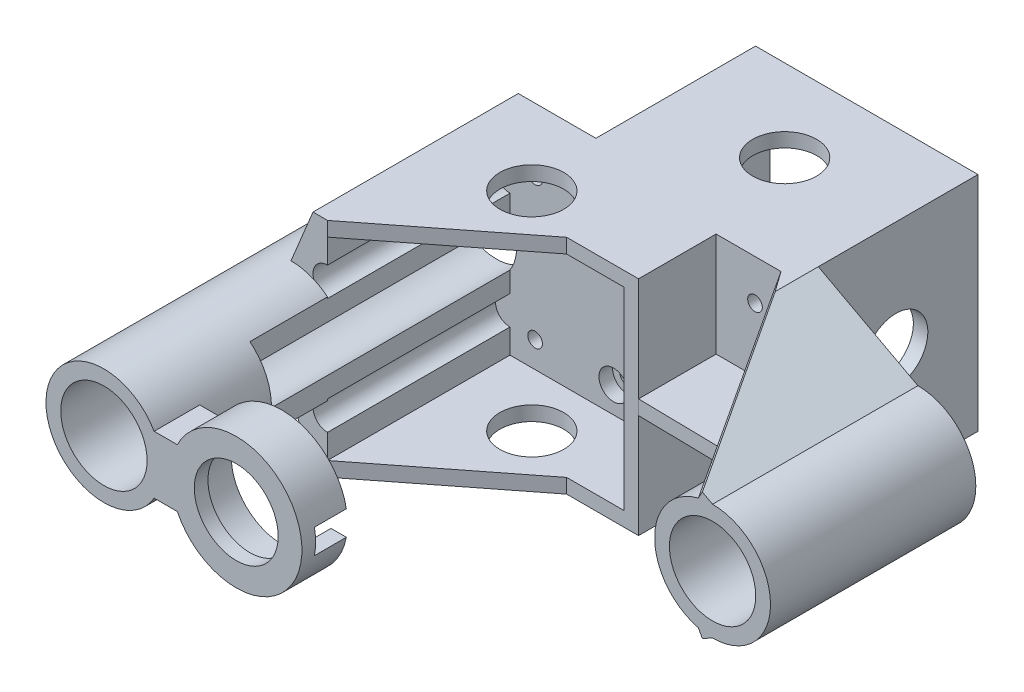
SolidWorks part; units mm, degrees
ref_plane "Front" through (0, 0, 0) normal (0, 0, 1) x (1, 0, 0)
ref_plane "Top" through (0, 0, 0) normal (0, 1, 0) x (1, 0, 0)
ref_plane "Right" through (0, 0, 0) normal (1, 0, 0) x (0, 0, -1)
sketch "Sketch4" plane through (0, 0, 0) normal (0, 0, 1) x (1, 0, 0)
  line L0 (0, -42.8625) -> (0, 41.275) construction
  line L1 (-47.9, -15.5) -> (-78.9, 15.5) construction
  line L2 (-78.9, -15.5) -> (-47.9, 15.5) construction
  line L3 (-39.225, 44.5615) -> (-39.225, -66.5635) construction
  line L4 (-70.575, 44.5615) -> (-70.575, -66.5635) construction
  line L8 (-61.7, 15.5) -> (-30.7, -15.5) construction
  line L9 (-30.7, 15.5) -> (-61.7, -15.5) construction
  line L11 (-30.7, 36.624) -> (-30.7, -53.8635) construction
  line L12 (45, 0) -> (-163.2133, 0) construction
  line L13 (-61.7, 36.624) -> (-61.7, -53.8635) construction
  line L14 (-47.9, 36.624) -> (-47.9, -53.8635) construction
  line L15 (-78.9, 36.624) -> (-78.9, -53.8635) construction
  line L16 (-111.9728, 15.5) -> (1.0464, 15.5) construction
  line L17 (-111.9728, -15.5) -> (1.0464, -15.5) construction
  line L18 (-25, -66.5635) -> (-25, 44.5615) construction
  line L19 (-67.4, -66.5635) -> (-67.4, 44.5615) construction
  line L20 (-42.4, 44.5615) -> (-42.4, -66.5635) construction
  line L21 (-84.4, -66.5635) -> (-84.4, 44.5615) construction
  line L22 (7.0897, -21.2) -> (-132.9126, -21.2) construction
  line L23 (7.0897, 21.2) -> (-132.9126, 21.2) construction
  line L24 (12.1749, -24.375) -> (-137.3728, -24.375) construction
  line L25 (12.1749, 24.375) -> (-137.3728, 24.375) construction
  line L26 (-87.575, 44.5615) -> (-87.575, -66.5635) construction
  line L27 (-21.825, 44.5615) -> (-21.825, -66.5635) construction
  circle A0 centre (0, 0) radius 12.7 construction
  circle A1 centre (0, 0) radius 15.875 construction
  circle A2 centre (0, 0) radius 9.46 construction
  circle A3 centre (-92.4, 0) radius 9.46 construction
  arc A4 (-92.4, 12.7) -> (-92.4, -12.7) centre (-92.4, 0) ccw construction
  circle A5 centre (27.62, 0) radius 9.46 construction
  circle A6 centre (27.62, 0) radius 12.7 construction
  circle A7 centre (-120.0175, 0) radius 9.46 construction
  circle A8 centre (-120.0175, 0) radius 12.7 construction
  point P3 (0, 0)
  point P6 (-47.9, -15.5)
  point P11 (-92.4, 0)
  point P12 (-47.9, 15.5)
  point P13 (-46.2, 0)
  point P14 (-78.9, 15.5)
  point P15 (-78.9, -15.5)
  point P61 (-63.4, 0)
  point P65 (27.62, 0)
  point P66 (-120.0175, 0)
  dimension "D20" = 3.175
  dimension "D18" = 29
  dimension "D26" = 73.82
  dimension "D27" = 63.4
  dimension "D2" = 31
  dimension "D3" = 25
  dimension "D4" = 31
  dimension "D5" = 21.825
  dimension "D6" = 15.5
  dimension "D7" = 15.5
  dimension "D8" = 5.7
  dimension "D9" = 5.7
  dimension "D10" = 5.5
  dimension "D11" = 5.5
  dimension "D12" = 5.7
  dimension "D13" = 5.7
  dimension "D14" = 3.175
  dimension "D15" = 3.175
  dimension "D16" = 3.175
  dimension "D17" = 3.175
  dimension "D19" = 3.175
  dimension "D21" = 3.175
  dimension "D22" = 46.2
  dimension "D23" = 46.2
  dimension "D24" = 58.32
  dimension "D25" = 147.6375
sketch "Sketch5" plane through (0, 0, 0) normal (0, 0, 1) x (1, 0, 0)
  line L0 (-21.825, -24.375) -> (0, -12.7)
  line L1 (12.1749, -24.375) -> (-137.3728, -24.375) construction
  line L2 (-21.825, 44.5615) -> (-21.825, -66.5635) construction
  line L3 (0, -42.8625) -> (0, 41.275) construction
  line L4 (12.1749, 24.375) -> (-137.3728, 24.375) construction
  line L5 (-21.825, 24.375) -> (0, 12.7)
  line L7 (-92.4, 12.7) -> (-87.575, 24.375)
  line L8 (-87.575, 44.5615) -> (-87.575, -66.5635) construction
  line L9 (-87.575, 24.375) -> (-21.825, 24.375)
  line L10 (-87.575, -24.375) -> (-92.4, -12.7)
  line L11 (-87.575, -24.375) -> (-21.825, -24.375)
  circle A0 centre (0, 0) radius 12.7 construction
  arc A1 (0, 12.7) -> (0, -12.7) centre (0, 0) cw
  circle A2 centre (0, 0) radius 9.46
  circle A3 centre (-92.4, 0) radius 9.46
  arc A4 (-92.4, 12.7) -> (-92.4, -12.7) centre (-92.4, 0) ccw
  circle A6 centre (-30.7, 15.5) radius 1.6
  circle A7 centre (-30.7, -15.5) radius 1.6
  circle A8 centre (-47.9, -15.5) radius 1.6
  circle A9 centre (-47.9, 15.5) radius 1.6
  circle A10 centre (-61.7, 15.5) radius 1.6
  circle A11 centre (-78.9, 15.5) radius 1.6
  circle A12 centre (-78.9, -15.5) radius 1.6
  circle A13 centre (-61.7, -15.5) radius 1.6
  arc A15 (-92.4, 12.7) -> (-92.4, -12.7) centre (-92.4, 0) ccw construction
extrude "Extrude1" add sketch "Sketch5" along normal blind 5
sketch "Sketch6" plane through (0, 0, 5) normal (0, 0, 1) x (1, 0, 0)
  line L0 (-84.4, -21.2) -> (-42.4, -21.2)
  line L1 (-84.4, -66.5635) -> (-84.4, 44.5615) construction
  line L2 (7.0897, -21.2) -> (-132.9126, -21.2) construction
  line L3 (-42.4, 44.5615) -> (-42.4, -66.5635) construction
  line L4 (-42.4, -21.2) -> (-42.4, 21.2)
  line L5 (7.0897, 21.2) -> (-132.9126, 21.2) construction
  line L6 (-42.4, 21.2) -> (-84.4, 21.2)
  line L7 (-39.225, 24.375) -> (-87.575, 24.375)
  line L9 (-39.225, 44.5615) -> (-39.225, -66.5635) construction
  line L10 (12.1749, 24.375) -> (-137.3728, 24.375) construction
  line L11 (-12.601, 1.5825) -> (-39.225, 1.5825)
  line L12 (-39.225, -24.375) -> (-87.575, -24.375)
  line L13 (-84.4, 21.2) -> (-84.4, 15.8916)
  line L14 (-84.4, -9.5084) -> (-84.4, -5.0489)
  line L16 (-87.575, 24.375) -> (-92.4, 12.7)
  line L17 (-87.575, -24.375) -> (-92.4, -12.7)
  line L19 (-84.4, 9.5416) -> (-84.4, 5.0489)
  line L20 (-84.4, -21.2) -> (-84.4, -15.8584)
  line L24 (-39.225, -1.5851) -> (-12.6007, -1.5851)
  line L25 (-39.225, 1.5825) -> (-39.225, 24.375)
  line L27 (-21.825, -24.375) -> (0, -12.7)
  line L28 (-21.825, 24.375) -> (0, 12.7)
  line L29 (-25, 24.375) -> (-3.1127, 12.3127)
  line L30 (-25, -66.5635) -> (-25, 44.5615) construction
  line L31 (-25, -24.375) -> (-3.1127, -12.3127)
  line L32 (12.1749, -24.375) -> (-137.3728, -24.375) construction
  line L33 (-25, -24.375) -> (-21.825, -24.375)
  line L34 (-39.225, -1.5851) -> (-39.225, -24.375)
  line L35 (-25, 24.375) -> (-21.825, 24.375)
  line L36 (0, -42.8625) -> (0, 41.275) construction
  circle A0 centre (-92.4, 0) radius 9.46 construction
  arc A1 (-92.4, 12.7) -> (-92.4, -12.7) centre (-92.4, 0) ccw
  arc A3 (-84.4, 5.0489) -> (-84.4, -5.0489) centre (-92.4, 0) ccw
  circle A4 centre (0, 0) radius 9.46
  circle A5 centre (0, 0) radius 12.7 construction
  arc A6 (0, -12.7) -> (0, 12.7) centre (0, 0) ccw
  arc A7 (-3.1127, 12.3127) -> (-12.601, 1.5825) centre (0, 0) ccw
  arc A8 (-3.1127, -12.3127) -> (-12.6007, -1.5851) centre (0, 0) cw
  arc A12 (-92.4, 12.7) -> (-92.4, -12.7) centre (-92.4, 0) ccw construction
  circle A13 centre (-84.4, 12.7166) radius 3.175 construction
  circle A14 centre (-84.4, -12.6834) radius 3.175 construction
  arc A15 (-84.4, 15.8916) -> (-84.4, 9.5416) centre (-84.4, 12.7166) ccw
  arc A16 (-84.4, -9.5084) -> (-84.4, -15.8584) centre (-84.4, -12.6834) ccw
  point P36 (-84.4, 12.7166)
  point P39 (-84.4, -12.6834)
extrude "Extrude2" add sketch "Sketch6" along normal blind 40
sketch "Sketch7" plane through (0, 0, 0) normal (0, 0, -1) x (-1, 0, 0)
  line L0 (25, -21.2) -> (25, 21.3719)
  line L1 (25, -66.5635) -> (25, 44.5615) construction
  line L2 (-7.0897, -21.2) -> (132.9126, -21.2) construction
  line L3 (25, 21.3719) -> (67.4, 21.2)
  line L4 (67.4, -66.5635) -> (67.4, 44.5615) construction
  line L5 (-7.0897, 21.2) -> (132.9126, 21.2) construction
  line L6 (67.4, 21.2) -> (67.4, -21.2)
  line L7 (67.4, -21.2) -> (25, -21.2)
  line L8 (21.825, 24.375) -> (21.825, -24.375)
  line L9 (21.825, 24.375) -> (70.575, 24.375)
  line L10 (70.575, 44.5615) -> (70.575, -66.5635) construction
  line L11 (-12.1749, 24.375) -> (137.3728, 24.375) construction
  line L12 (70.575, 24.375) -> (70.575, -24.375)
  line L13 (-12.1749, -24.375) -> (137.3728, -24.375) construction
  line L14 (70.575, -24.375) -> (21.825, -24.375)
extrude "Extrude3" add sketch "Sketch7" along normal blind 35
sketch "Sketch12" plane through (4.4797, 8.1284, 0) normal (-0.4827, -0.8758, 0) x (0, 0, 1)
  line L0 (45, 8.669) -> (5, 33.6601)
  line L1 (5, 33.6601) -> (45, 33.6601)
  line L2 (45, 33.6601) -> (45, 8.669)
extrude "Extrude5" cut sketch "Sketch12" against normal up to surface (1.4977 mm away) up to face at (-10.9125, 18.5375, 22.5)
sketch "Sketch13" plane through (4.4797, -8.1284, 0) normal (-0.4827, 0.8758, 0) x (0, 0, 1)
  line L0 (45, -8.669) -> (5, -33.6601)
  line L1 (5, -33.6601) -> (45, -33.6601)
  line L2 (45, -33.6601) -> (45, -8.669)
extrude "Extrude6" cut sketch "Sketch13" against normal up to surface (1.4977 mm away) up to face at (-10.9125, -18.5375, 22.5)
sketch "Sketch16" plane through (0, -24.375, 0) normal (0, -1, 0) x (1, 0, 0)
  line L0 (-39.225, 5) -> (-39.225, 22) construction
  line L1 (-39.225, 45) -> (-39.225, 5) construction
  line L2 (-39.225, 22) -> (-16.782, 22.4034)
  line L3 (-16.782, 22.4034) -> (-12.6007, 29.0539)
  line L4 (-12.6007, 45) -> (-12.6007, 5) construction
  line L5 (-12.6007, 29.0539) -> (-12.6007, 45)
  line L6 (-12.6007, 45) -> (-84.4, 45)
  line L7 (-84.4, 45) -> (-54.9816, 22)
  line L8 (-54.9816, 22) -> (-39.225, 22)
  line L9 (-46.2, 0) -> (-46.2, -39.1338) construction
  line L10 (-67.6181, 0) -> (-67.6181, 27.6964) construction
  line L11 (12.1749, 0) -> (-137.3728, 0) construction
  circle A0 centre (-46.2, -17) radius 7
  circle A1 centre (-67.6181, 17) radius 7
extrude "Extrude9" cut sketch "Sketch16" against normal up to surface (48.75 mm away) up to face at (-47.12, 24.375, 3.9725)
sketch "Sketch17" plane through (0, 0, 45) normal (0, 0, 1) x (1, 0, 0)
  line L1 (-84.4, -66.5635) -> (-84.4, 44.5615) construction
  line L2 (-84.4, 9.8636) -> (-84.4, 5.0489)
  line L3 (-84.4, -5.0489) -> (-84.4, -9.8636)
  arc A0 (-84.4, 5.0489) -> (-84.4, -5.0489) centre (-92.4, 0) ccw
  arc A1 (-92.4, 12.7) -> (-92.4, -12.7) centre (-92.4, 0) ccw
  arc A2 (-92.4, 12.7) -> (-92.4, -12.7) centre (-92.4, 0) ccw construction
  arc A3 (-92.4, -12.7) -> (-84.4, -9.8636) centre (-92.4, 0) ccw
  arc A4 (-92.4, 12.7) -> (-84.4, 9.8636) centre (-92.4, 0) cw
extrude "Extrude10" add sketch "Sketch17" along normal blind 17
sketch "Sketch18" plane through (0, 0, 62) normal (0, 0, 1) x (1, 0, 0)
  circle A0 centre (-92.4, 0) radius 9.46
  circle A1 centre (-92.4, 0) radius 12.7
extrude "Extrude11" add sketch "Sketch18" along normal blind 14
sketch "Sketch19" plane through (0, 0, 76) normal (0, 0, 1) x (1, 0, 0)
  line L0 (-81.3983, -6.3446) -> (-76.3158, -6.3446)
  line L1 (-81.3983, 6.3446) -> (-76.3158, 6.3446)
  circle A0 centre (-63.4, 0) radius 11.1
  circle A1 centre (-63.4, 0) radius 14.39 construction
  circle A2 centre (-92.4, 0) radius 9.46
  circle A3 centre (-92.4, 0) radius 12.7 construction
  arc A4 (-76.3158, -6.3446) -> (-76.3158, 6.3446) centre (-63.4, 0) ccw
  arc A5 (-81.3983, 6.3446) -> (-81.3983, -6.3446) centre (-92.4, 0) ccw
extrude "Extrude12" add sketch "Sketch19" along normal blind 7
sketch "Sketch20" plane through (0, 0, 83) normal (0, 0, 1) x (1, 0, 0)
  line L0 (-81.3983, -6.3446) -> (-76.3158, -6.3446) construction
  line L1 (-81.3983, 6.3446) -> (-76.3158, 6.3446)
  line L2 (-81.3983, -6.3446) -> (-76.3158, -6.3446)
  circle A0 centre (-92.4, 0) radius 9.46
  circle A1 centre (-92.4, 0) radius 12.7 construction
  circle A2 centre (-63.4, 0) radius 14.39 construction
  arc A3 (-81.3983, 6.3446) -> (-81.3983, -6.3446) centre (-92.4, 0) ccw
  arc A4 (-76.3158, -6.3446) -> (-76.3158, 6.3446) centre (-63.4, 0) ccw
  circle A5 centre (-63.4, 0) radius 9.2
extrude "Extrude13" add sketch "Sketch20" along normal blind 3
sketch "Sketch21" plane through (-42.4, 0, 0) normal (-1, 0, 0) x (0, 0, 1)
  line L0 (76, 0) -> (76, -2.7)
  line L1 (76, 6.3446) -> (76, -6.3446) construction
  line L2 (76, 0) -> (76, 2.7)
  line L3 (76, -2.7) -> (83, -2.7)
  line L4 (83, 11.1) -> (83, -11.1) construction
  line L5 (83, -2.7) -> (83, 2.7)
  line L6 (83, 2.7) -> (76, 2.7)
extrude "Extrude14" cut sketch "Sketch21" along normal blind 15
sketch "Sketch22" plane through (0, 0, 5) normal (0, 0, 1) x (1, 0, 0)
  circle A0 centre (-61.7, 15.5) radius 3.2
  circle A1 centre (-61.7, -15.5) radius 3.2
extrude "Extrude15" cut sketch "Sketch22" against normal blind 3
sketch "Sketch23" plane through (0, 0, 0) normal (0, 0, -1) x (-1, 0, 0)
  circle A0 centre (47.9, 15.5) radius 3.2
  circle A1 centre (47.9, -15.5) radius 3.2
extrude "Extrude16" cut sketch "Sketch23" against normal blind 3
sketch "Sketch24" plane through (-70.575, 0, 0) normal (-1, 0, 0) x (0, 0, 1)
  line L0 (0, 0) -> (0, 4)
  line L1 (0, -66.5635) -> (0, 44.5615) construction
  line L2 (0, 0) -> (0, -4)
  circle A0 centre (-17, 0) radius 7
  arc A1 (0, 4) -> (0, -4) centre (0, 0) ccw
extrude "Extrude17" cut sketch "Sketch24" against normal up to surface (48.75 mm away) up to face at (-21.825, 0, -17.5)
